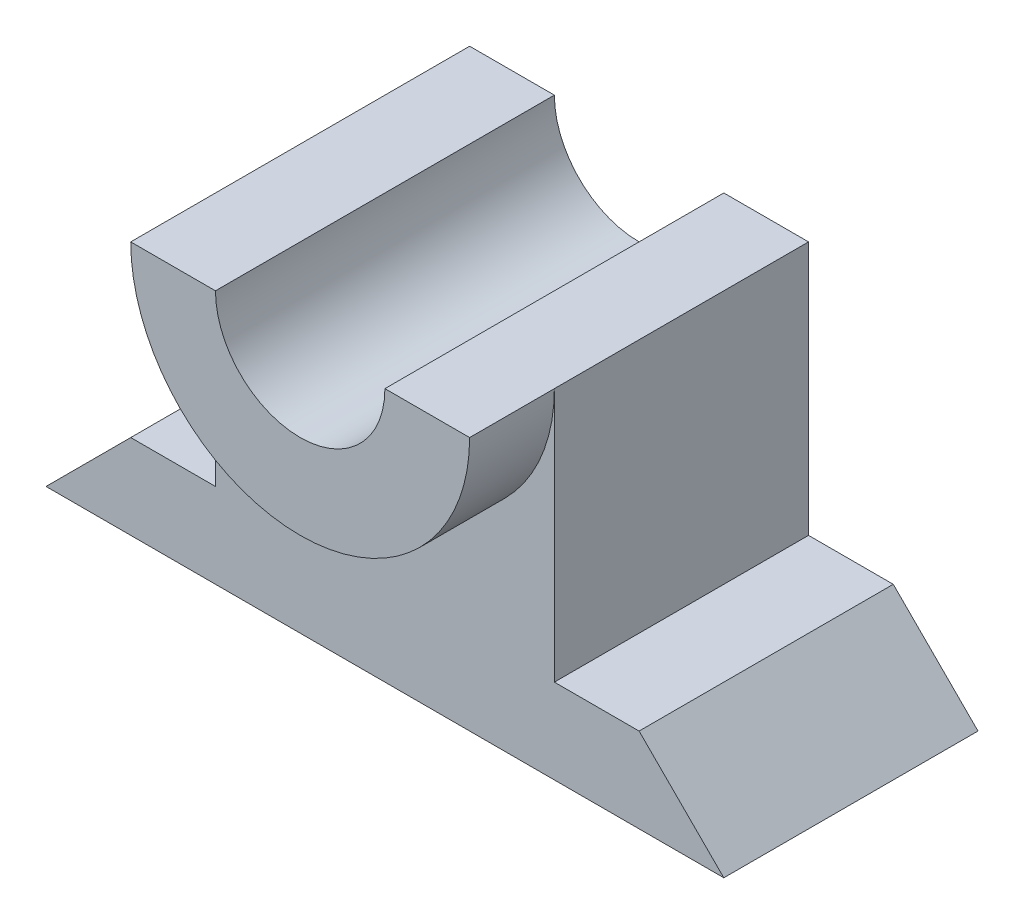
SolidWorks part; units mm, degrees
ref_plane "前基準面" through (0, 0, 0) normal (0, 0, 1) x (1, 0, 0)
ref_plane "上基準面" through (0, 0, 0) normal (0, 1, 0) x (1, 0, 0)
ref_plane "右基準面" through (0, 0, 0) normal (1, 0, 0) x (0, 0, -1)
sketch "草圖1" plane through (0, 0, 0) normal (0, 0, 1) x (1, 0, 0)
  line L0 (0, 19.53) -> (0, -19.53) construction
  line L1 (0, 0) -> (4, 0)
  line L2 (4, 0) -> (3, 1)
  line L3 (3, 1) -> (2, 1)
  line L4 (2, 1) -> (2, 4)
  line L5 (2, 4) -> (0, 4)
  line L6 (0, 4) -> (0, 0)
  point P4 (0, 0)
  dimension "D1" = 4
  dimension "D2" = 1
  dimension "D3" = 1
  dimension "D4" = 4
  dimension "D5" = 2
extrude "填料-伸長1" add sketch "草圖1" along normal blind 3
sketch "草圖2" plane through (0, 0, 0) normal (0, 0, 1) x (1, 0, 0)
  line L0 (0, 0) -> (0, 4) construction
  line L1 (2, 4) -> (0, 4)
  line L2 (0, 4) -> (0, 2)
  arc A0 (0, 3) -> (1, 4) centre (0, 4) ccw
  arc A1 (0, 2) -> (2, 4) centre (0, 4) ccw
  dimension "D1" = 2
extrude "填料-伸長2" add sketch "草圖2" along normal blind 4 contours L2 A1 L1 A0 region at (0.9903, 3.0097, 0)
extrude "除料-伸長1" cut sketch "草圖2<3>" along normal blind 4 contours L2 A0 L1 region at (0.4244, 3.5756, 0)
sketch "草圖2<3>" plane through (0, 0, 0) normal (0, 0, 1) x (1, 0, 0) same geometry as "草圖2"
mirror "鏡射1" about plane through (0, 0, 0) normal (1, 0, 0) of "除料-伸長1", "填料-伸長2", "填料-伸長1"
